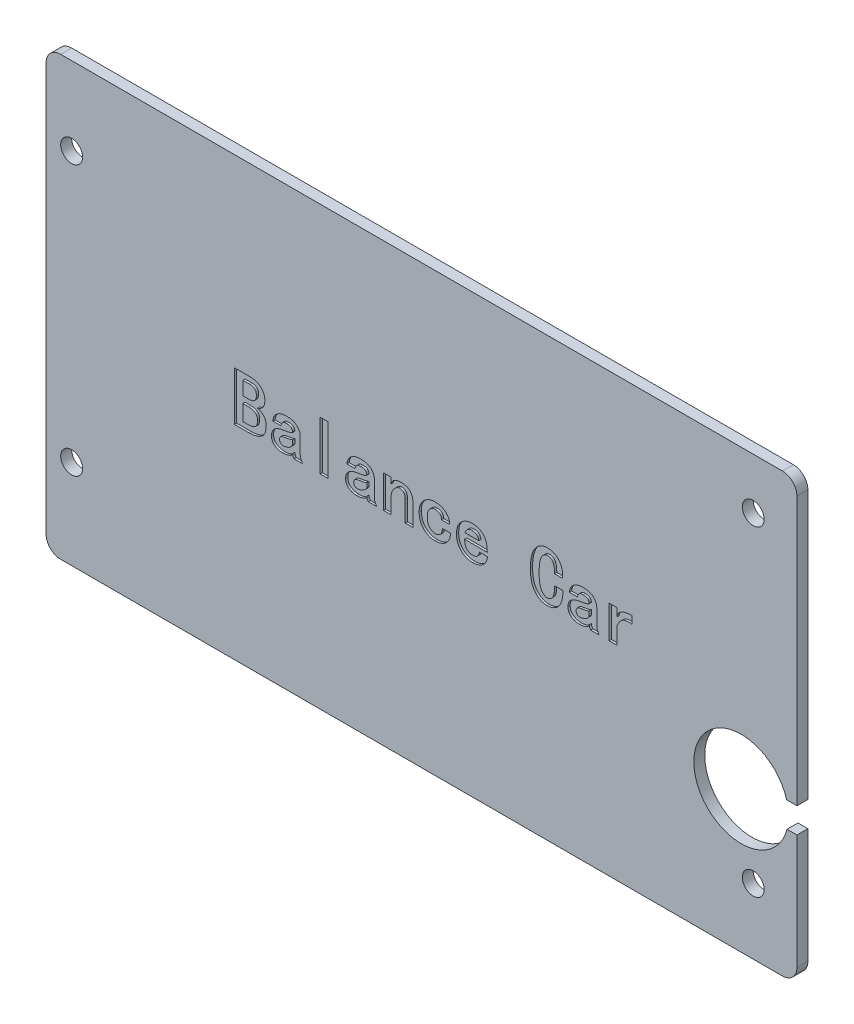
SolidWorks part; units mm, degrees
ref_plane "前视基准面" through (0, 0, 0) normal (0, 0, 1) x (1, 0, 0)
ref_plane "上视基准面" through (0, 0, 0) normal (0, 1, 0) x (1, 0, 0)
ref_plane "右视基准面" through (0, 0, 0) normal (1, 0, 0) x (0, 0, -1)
sketch "草图1" plane through (0, 0, 0) normal (0, 0, 1) x (1, 0, 0)
  line L0 (26.8171, -30.979) -> (26.8171, -46.7301)
  line L1 (-74.1829, 11.2699) -> (24.8171, 11.2699)
  line L2 (-76.1829, 9.2699) -> (-76.1829, -46.7301)
  line L3 (-74.1829, -48.7301) -> (24.8171, -48.7301)
  line L4 (26.8171, 9.2699) -> (26.8171, -27.5074)
  line L5 (25.4069, -27.5074) -> (26.8171, -27.5074)
  line L7 (25.4583, -30.979) -> (26.8171, -30.979)
  line L10 (-76.1829, -18.7301) -> (26.8171, -18.7301) construction
  circle A2 centre (20.8171, 4.2699) radius 1.5
  arc A3 (25.4069, -27.5074) -> (25.4583, -30.979) centre (19.1694, -29.3358) ccw
  circle A4 centre (-72.6829, 0.5476) radius 1.5
  circle A6 centre (-72.6829, -36.4524) radius 1.5
  circle A12 centre (20.8171, -39.7301) radius 1.5
  arc A20 (-74.1829, 11.2699) -> (-76.1829, 9.2699) centre (-74.1829, 9.2699) ccw
  arc A21 (-74.1829, -48.7301) -> (-76.1829, -46.7301) centre (-74.1829, -46.7301) cw
  arc A22 (24.8171, -48.7301) -> (26.8171, -46.7301) centre (24.8171, -46.7301) ccw
  arc A23 (26.8171, 9.2699) -> (24.8171, 11.2699) centre (24.8171, 9.2699) ccw
  point P22 (25.5137, -27.5074)
  point P23 (26.8171, -27.5074)
  point P24 (26.8171, -30.979)
  point P30 (25.4583, -30.979)
  point P50 (8.726, -18.7301)
  point P56 (-76.1829, 11.2699)
  point P61 (26.8171, -48.7301)
  point P64 (26.8171, 11.2699)
  dimension "D19" = 2
  dimension "D9" = 13
  dimension "D3" = 37
  dimension "D5" = 60
  dimension "D6" = 44
  dimension "D7" = 6
  dimension "D8" = 7
  dimension "D13" = 103
  dimension "D16" = 3.5
extrude "凸台-拉伸1" add sketch "草图1" along normal blind 1.5
sketch "草图2" plane through (0, 0, 1.5) normal (0, 0, 1) x (1, 0, 0)
  text T0 "<b>Balance Car</b>" font "黑体" height in points 22
extrude "切除-拉伸1" cut sketch "草图2" against normal blind 0.3
